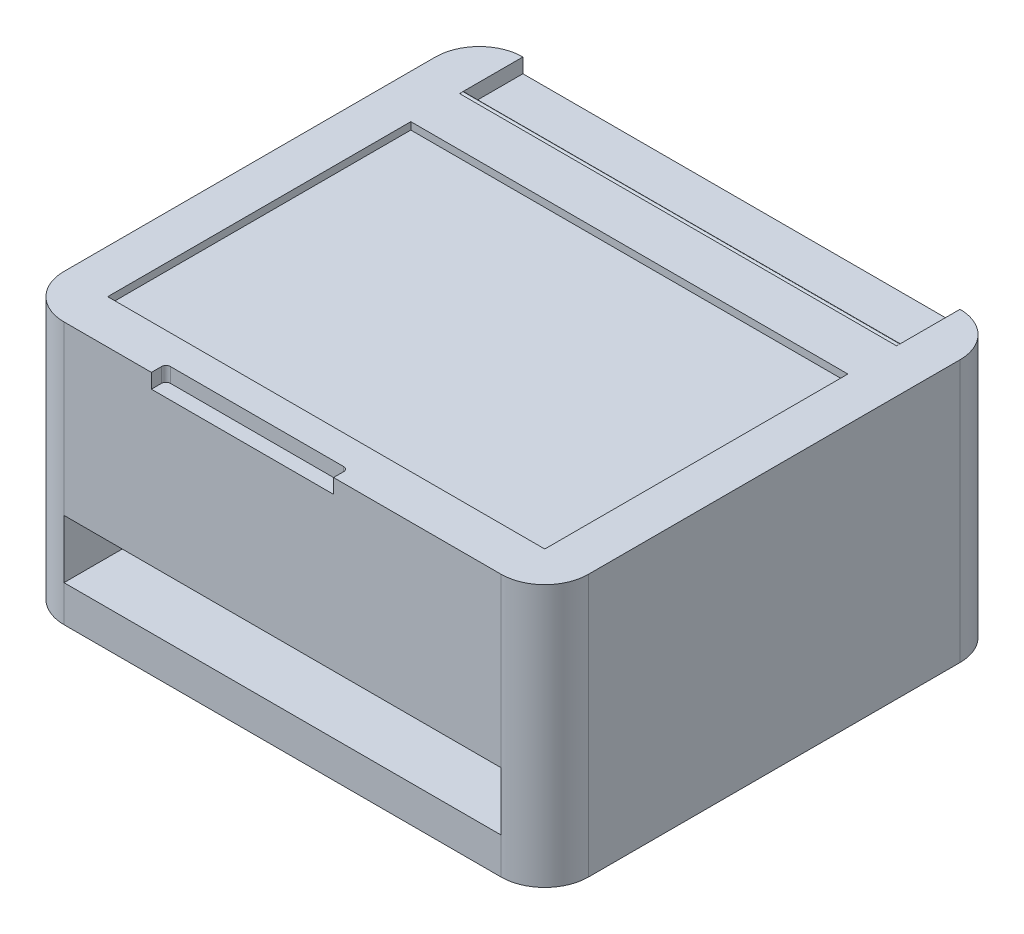
SolidWorks part; units mm, degrees
note: The reader was unsure of these and kept them because the rebuilt part matched: thickness of "Base-Flange1", "Sheet-Metal1", "Sheet-Metal2", "Sheet-Metal3", "Sheet-Metal6", "Sheet-Metal8", "Sheet-Metal10".
ref_plane "Front Plane" through (0, 0, 0) normal (0, 0, 1) x (1, 0, 0)
ref_plane "Top Plane" through (0, 0, 0) normal (0, 1, 0) x (1, 0, 0)
ref_plane "Right Plane" through (0, 0, 0) normal (1, 0, 0) x (0, 0, -1)
sketch "Sketch1" plane through (0, 0, 0) normal (0, 1, 0) x (1, 0, 0)
  line L1 (180, -157.5) -> (-180, -157.5)
  line L2 (180, -157.5) -> (180, 157.5)
  line L3 (180, 157.5) -> (-180, 157.5)
  line L4 (-180, -157.5) -> (-180, 157.5)
  line L5 (180, -157.5) -> (-180, 157.5) construction
  line L6 (180, 157.5) -> (-180, -157.5) construction
  point P0 (0, 0)
  dimension "D1" = 360
  dimension "D2" = 315
base flange "Base-Flange1" sketch "Sketch1" thickness 180 reverse thickness direction no parameters "D1"=0.7366
fillet "Fillet1" radius 30 4 edges at (-180, -90, 157.5) (-180, -90, -157.5) (180, -90, -157.5) (180, -90, 157.5)
sketch "Sketch6" plane through (0, 0, 0) normal (0, 1, 0) x (1, 0, 0)
  line L0 (-150, 157.5) -> (-150, 117.5)
  line L1 (150, 157.5) -> (-150, 157.5) construction
  line L2 (-150, 117.5) -> (150, 117.5)
  line L3 (150, 117.5) -> (150, 157.5)
  line L4 (-180, 127.5) -> (-180, -127.5) construction
  line L5 (180, -127.5) -> (180, 127.5) construction
  line L6 (-150, 157.5) -> (150, 157.5)
  dimension "D1" = 40
  dimension "D2" = 30
  dimension "D3" = 30
extrude "Cut-Extrude1" cut sketch "Sketch6" against normal blind 10 normal cut yes
sketch "Sketch7" plane through (0, 0, 0) normal (0, 1, 0) x (1, 0, 0)
  line L0 (-90, -157.5) -> (-90, -150.5)
  line L1 (-150, -157.5) -> (150, -157.5) construction
  line L2 (-87, -147.5) -> (32, -147.5)
  line L3 (35, -150.5) -> (35, -157.5)
  line L4 (-90, -157.5) -> (35, -157.5)
  line L5 (-180, 127.5) -> (-180, -127.5) construction
  line L6 (180, -127.5) -> (180, 127.5) construction
  arc A0 (32, -147.5) -> (35, -150.5) centre (32, -150.5) cw
  arc A1 (-90, -150.5) -> (-87, -147.5) centre (-87, -150.5) cw
  point P14 (-90, -147.5)
  dimension "D4" = 3
  dimension "D1" = 90
  dimension "D2" = 145
  dimension "D3" = 10
extrude "Cut-Extrude2" cut sketch "Sketch7" against normal blind 10 normal cut yes
sketch "Sketch16" plane through (0, 0, 0) normal (0, 1, 0) x (1, 0, 0)
  line L0 (-150, 117.5) -> (150, 117.5)
  line L1 (-150, 117.5) -> (-150, 113.98)
  line L2 (150, 117.5) -> (150, 113.98)
  line L3 (-150, 113.98) -> (150, 113.98)
  dimension "D1" = 3.52
extrude "Cut-Extrude3" cut sketch "Sketch16" against normal blind 3.52 normal cut yes
sketch "Sketch17" plane through (-150, 0, 0) normal (1, 0, 0) x (0, 0, -1)
  line L0 (117.5, -3.52) -> (113.98, -3.52) construction
  line L1 (113.98, -3.52) -> (113.98, 0) construction
  circle A0 centre (115.74, -1.76) radius 1.76
  dimension "D1" = 1.76
  dimension "D2" = 1.76
extrude "Boss-Extrude3" add sketch "Sketch17" along normal blind 300 separate body
sketch "Sketch18" plane through (0, 0, 157.5) normal (0, 0, 1) x (1, 0, 0)
  line L0 (-150, -155) -> (-150, -115)
  line L1 (-150, -155) -> (150, -155)
  line L2 (-150, -115) -> (150, -115)
  line L3 (150, -155) -> (150, -115)
  line L4 (-150, 0) -> (-150, -180) construction
  line L5 (150, -180) -> (150, 0) construction
  line L6 (-150, -180) -> (150, -180) construction
  dimension "D1" = 40
  dimension "D2" = 25
extrude "Cut-Extrude4" cut sketch "Sketch18" against normal blind 150
sketch "Sketch22" plane through (0, 0, 0) normal (0, 1, 0) x (1, 0, 0)
  line L0 (-150, 80.5482) -> (-150, -127.5)
  line L1 (-150, -127.5) -> (150, -127.5)
  line L2 (150, -127.5) -> (150, 80.5482)
  line L3 (150, 80.5482) -> (-150, 80.5482)
extrude "Cut-Extrude6" cut sketch "Sketch22" against normal blind 5
sketch "Bend-Lines1" [suppressed] plane through (0, 0, 0) normal (0, 1, 0) x (1, 0, 0)
sketch "Bounding-Box1" [suppressed] plane through (0, 0, 0) normal (0, 1, 0) x (1, 0, 0)
sheet metal parameters "Sheet-Metal1" thickness 180 parameters "D1"=0.7366
flat pattern "Flat-Pattern1" [suppressed]
sketch "Bend-Lines2" plane through (0, 0, 0) normal (0, 1, 0) x (1, 0, 0)
sketch3d "Bounding-Box2" [suppressed]
  line L0 (-180, -157.5, 0) -> (180, -157.5, 0) construction
  line L1 (-180, 157.5, 0) -> (180, 157.5, 0) construction
  line L2 (-180, -157.5, 0) -> (-180, 157.5, 0) construction
  line L3 (180, -157.5, 0) -> (180, 157.5, 0) construction
sheet metal parameters "Sheet-Metal2" thickness 180 parameters "D1"=0.7366, "D7"=0.75
flat pattern "Flat-Pattern1"
sketch "Bend-Lines2" plane through (0, 0, 0) normal (0, 1, 0) x (1, 0, 0)
sketch3d "Bounding-Box2" [suppressed]
  line L0 (-180, -157.5, 0) -> (180, -157.5, 0) construction
  line L1 (-180, 157.5, 0) -> (180, 157.5, 0) construction
  line L2 (-180, -157.5, 0) -> (-180, 157.5, 0) construction
  line L3 (180, -157.5, 0) -> (180, 157.5, 0) construction
sheet metal parameters "Sheet-Metal3" thickness 180 parameters "D1"=0.7366, "D7"=0.75
flat pattern "Flat-Pattern1"
sketch "Bend-Lines2" plane through (0, 0, 0) normal (0, 1, 0) x (1, 0, 0)
sketch3d "Bounding-Box2" [suppressed]
  line L0 (-180, -157.5, 0) -> (180, -157.5, 0) construction
  line L1 (-180, 157.5, 0) -> (180, 157.5, 0) construction
  line L2 (-180, -157.5, 0) -> (-180, 157.5, 0) construction
  line L3 (180, -157.5, 0) -> (180, 157.5, 0) construction
sheet metal parameters "Sheet-Metal6" thickness 180 parameters "D1"=0.7366, "D7"=0.75
flat pattern "Flat-Pattern1"
sketch "Bend-Lines2" plane through (0, 0, 0) normal (0, 1, 0) x (1, 0, 0)
sketch3d "Bounding-Box2" [suppressed]
  line L0 (-180, -157.5, 0) -> (180, -157.5, 0) construction
  line L1 (-180, 157.5, 0) -> (180, 157.5, 0) construction
  line L2 (-180, -157.5, 0) -> (-180, 157.5, 0) construction
  line L3 (180, -157.5, 0) -> (180, 157.5, 0) construction
sheet metal parameters "Sheet-Metal8" thickness 180 parameters "D1"=0.7366, "D7"=0.75
flat pattern "Flat-Pattern1"
sketch "Bend-Lines2" plane through (0, 0, 0) normal (0, 1, 0) x (1, 0, 0)
sketch3d "Bounding-Box2" [suppressed]
  line L0 (-180, -157.5, 0) -> (180, -157.5, 0) construction
  line L1 (-180, 157.5, 0) -> (180, 157.5, 0) construction
  line L2 (-180, -157.5, 0) -> (-180, 157.5, 0) construction
  line L3 (180, -157.5, 0) -> (180, 157.5, 0) construction
sheet metal parameters "Sheet-Metal10" thickness 180 parameters "D1"=0.7366, "D7"=0.75
flat pattern "Flat-Pattern1"
sketch "Bend-Lines2" plane through (0, 0, 0) normal (0, 1, 0) x (1, 0, 0)
sketch3d "Bounding-Box2" [suppressed]
  line L0 (-180, -157.5, 0) -> (180, -157.5, 0) construction
  line L1 (-180, 157.5, 0) -> (180, 157.5, 0) construction
  line L2 (-180, -157.5, 0) -> (-180, 157.5, 0) construction
  line L3 (180, -157.5, 0) -> (180, 157.5, 0) construction
